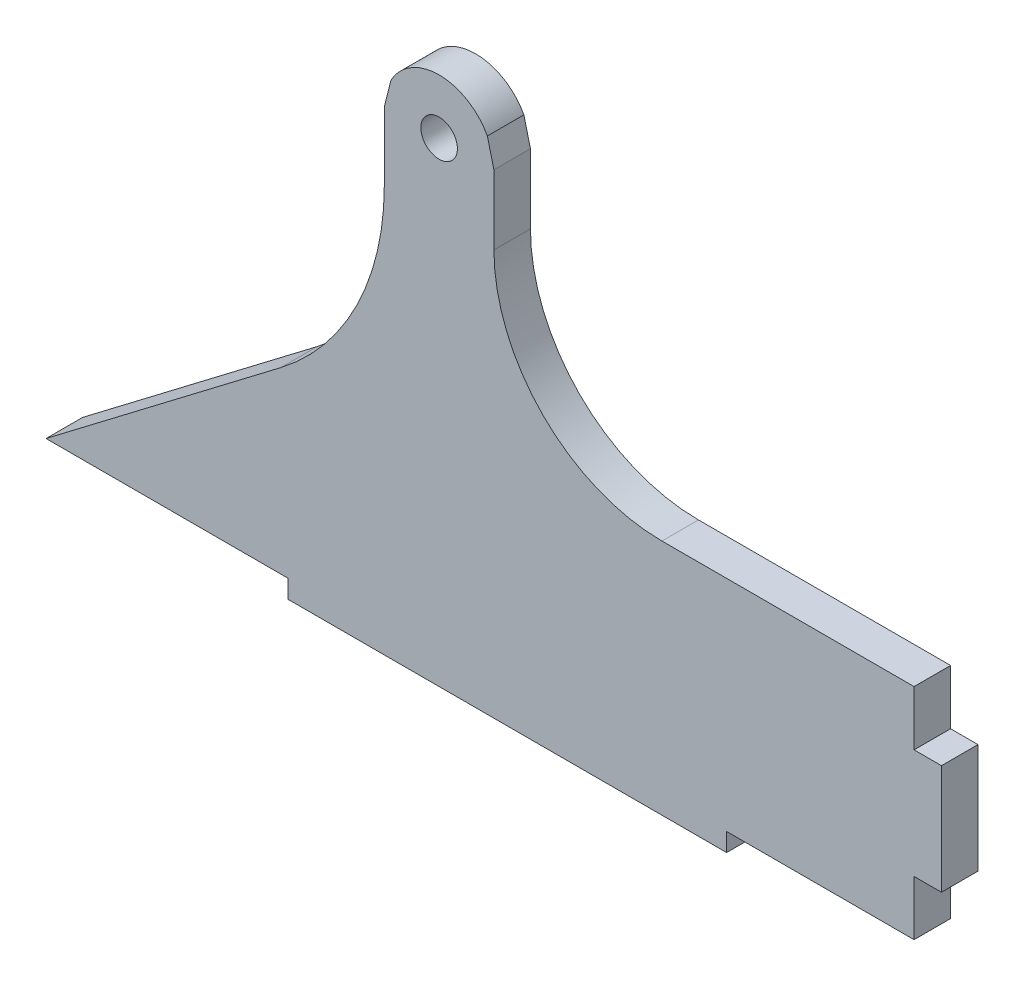
SolidWorks part; units mm, degrees
ref_plane "Front Plane" through (0, 0, 0) normal (0, 0, 1) x (1, 0, 0)
ref_plane "Top Plane" through (0, 0, 0) normal (0, 1, 0) x (1, 0, 0)
ref_plane "Right Plane" through (0, 0, 0) normal (1, 0, 0) x (0, 0, -1)
sketch "Sketch1" plane through (0, 0, 0) normal (0, 0, 1) x (1, 0, 0)
  line L0 (129.8035, 32.7787) -> (104.4035, 32.7787)
  line L1 (-171.9485, -43.4213) -> (-87.7475, -43.4213)
  line L4 (129.8035, -43.4213) -> (129.8035, -24.3713)
  line L5 (-171.9485, -43.4213) -> (129.8035, 32.7787) construction
  line L6 (-90.3867, 18.6912) -> (-171.9485, -43.4213)
  line L7 (-87.7475, -43.4213) -> (-87.7475, -49.7713)
  line L8 (-87.7475, -49.7713) -> (64.6525, -49.7713)
  line L9 (64.6525, -49.7713) -> (64.6525, -43.4213)
  line L16 (64.6525, -43.4213) -> (129.8035, -43.4213)
  line L17 (129.8035, 13.7287) -> (139.3285, 13.7287)
  line L18 (129.8035, 13.7287) -> (129.8035, 32.7787)
  line L19 (139.3285, -24.3713) -> (129.8035, -24.3713)
  line L20 (139.3285, 13.7287) -> (139.3285, -24.3713) construction
  line L21 (139.3285, 13.7287) -> (139.3285, -24.3713)
  line L23 (-16.2465, 115.3287) -> (-18.5281, 124.3689)
  line L24 (-61.2293, -49.7713) -> (-16.6946, -49.7713)
  line L27 (-52.0648, 124.3689) -> (-54.3465, 115.3287)
  line L29 (104.4035, 32.7787) -> (44.0785, 32.7787)
  line L30 (-16.2465, 91.1987) -> (-16.2465, 115.3287)
  line L31 (44.0785, 32.7787) -> (42.1735, 32.7787)
  line L32 (-54.3465, 115.3287) -> (-54.3465, 91.4383)
  line L33 (-54.3465, 91.4383) -> (-54.3465, 115.3287)
  line L34 (-16.2465, 115.3287) -> (-16.2465, 91.1987)
  line L36 (89.2905, 32.7787) -> (51.1905, 32.7787)
  circle A1 centre (-35.2965, 115.3287) radius 6.35
  arc A3 (-16.2465, 115.3287) -> (-54.3465, 115.3287) centre (-35.2965, 115.3287) ccw
  arc A5 (42.1735, 32.7787) -> (-16.2465, 91.1987) centre (42.1735, 91.1987) cw
  arc A6 (-54.3465, 91.4383) -> (-90.3867, 18.6912) centre (-145.7865, 91.4383) cw
  point P0 (0, 0)
  dimension "D13" = 165.1
  dimension "D14" = 12.7
  dimension "D15" = 165.1
  dimension "D16" = 58.42
  dimension "D7" = 91.44
  dimension "D2" = 301.752
  dimension "D3" = 76.2
  dimension "D4" = 6.35
  dimension "D5" = 152.4
  dimension "D6" = 38.1
  dimension "2.565" = 65.151
  dimension "D9" = 9.525
  dimension "D10" = 165.1
  dimension "D11" = 19.05
  dimension "D12" = 38.1
  dimension "D18" = 0
extrude "Boss-Extrude1" add sketch "Sketch1" along normal blind 12.7
